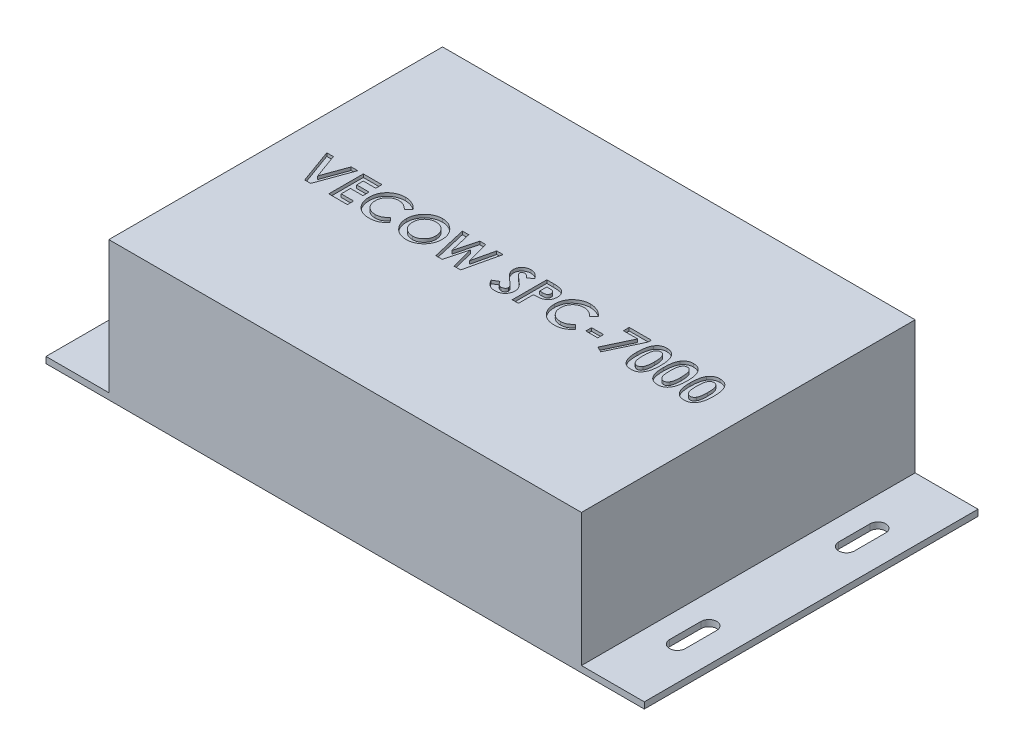
SolidWorks part; units mm, degrees
ref_plane "Front Plane" through (0, 0, 0) normal (0, 0, 1) x (1, 0, 0)
ref_plane "Top Plane" through (0, 0, 0) normal (0, 1, 0) x (1, 0, 0)
ref_plane "Right Plane" through (0, 0, 0) normal (1, 0, 0) x (0, 0, -1)
sketch "Sketch1" plane through (0, 0, 0) normal (0, 1, 0) x (1, 0, 0)
  line L1 (-75.2, 53.1) -> (75.2, 53.1)
  line L2 (-75.2, 53.1) -> (-75.2, -53.1)
  line L3 (-75.2, -53.1) -> (75.2, -53.1)
  line L4 (75.2, 53.1) -> (75.2, -53.1)
  line L5 (-75.2, 53.1) -> (75.2, -53.1) construction
  line L6 (-75.2, -53.1) -> (75.2, 53.1) construction
  point P0 (0, 0)
  dimension "D1" = 150.4
  dimension "D2" = 106.2
extrude "Boss-Extrude1" add sketch "Sketch1" along normal blind 44.2
sketch "Sketch2" plane through (75.2, 0, 0) normal (1, 0, 0) x (0, 0, -1)
  line L0 (53.1, 44.2) -> (53.1, 0) construction
  line L1 (-53.1, 0) -> (53.1, 0)
  line L2 (-53.1, 0) -> (-53.1, 2)
  line L3 (-53.1, 2) -> (53.1, 2)
  line L4 (53.1, 0) -> (53.1, 2)
  dimension "D1" = 2
extrude "Boss-Extrude2" add sketch "Sketch2" along normal blind 20
mirror "Mirror1" about plane through (0, 0, 0) normal (1, 0, 0) of "Boss-Extrude2"
sketch "Sketch3" plane through (0, 0, 0) normal (0, -1, 0) x (1, 0, 0)
  line L0 (-84.55, 31.9) -> (-84.55, 21.9) construction
  line L1 (-82.05, 31.9) -> (-82.05, 21.9)
  line L2 (-87.05, 31.9) -> (-87.05, 21.9)
  line L3 (-84.55, -21.9) -> (-84.55, -31.9) construction
  line L4 (-82.05, -21.9) -> (-82.05, -31.9)
  line L5 (-84.55, 26.9) -> (84.55, 26.9) construction
  line L6 (-84.55, 26.9) -> (-84.55, -26.9) construction
  line L7 (-84.55, -26.9) -> (84.55, -26.9) construction
  line L8 (84.55, 26.9) -> (84.55, -26.9) construction
  line L9 (-84.55, 26.9) -> (84.55, -26.9) construction
  line L10 (-84.55, -26.9) -> (84.55, 26.9) construction
  line L11 (-87.05, -21.9) -> (-87.05, -31.9)
  line L12 (84.55, 31.9) -> (84.55, 21.9) construction
  line L13 (87.05, 31.9) -> (87.05, 21.9)
  line L14 (82.05, 31.9) -> (82.05, 21.9)
  line L15 (84.55, -21.9) -> (84.55, -31.9) construction
  line L16 (87.05, -21.9) -> (87.05, -31.9)
  line L17 (82.05, -21.9) -> (82.05, -31.9)
  arc A0 (-82.05, 31.9) -> (-87.05, 31.9) centre (-84.55, 31.9) ccw
  arc A1 (-87.05, 21.9) -> (-82.05, 21.9) centre (-84.55, 21.9) ccw
  arc A2 (-82.05, -21.9) -> (-87.05, -21.9) centre (-84.55, -21.9) ccw
  arc A3 (-87.05, -31.9) -> (-82.05, -31.9) centre (-84.55, -31.9) ccw
  arc A4 (87.05, 31.9) -> (82.05, 31.9) centre (84.55, 31.9) ccw
  arc A5 (82.05, 21.9) -> (87.05, 21.9) centre (84.55, 21.9) ccw
  arc A6 (87.05, -21.9) -> (82.05, -21.9) centre (84.55, -21.9) ccw
  arc A7 (82.05, -31.9) -> (87.05, -31.9) centre (84.55, -31.9) ccw
  point P0 (0, 0)
  point P7 (-84.55, 26.9)
  point P14 (-84.55, -26.9)
  point P22 (84.55, 26.9)
  point P29 (84.55, -26.9)
  dimension "D3" = 2.5
  dimension "D1" = 169.1
  dimension "D2" = 53.8
  dimension "D4" = 10
extrude "Cut-Extrude1" cut sketch "Sketch3" against normal blind 20
sketch "Sketch4" plane through (0, 44.2, 0) normal (0, 1, 0) x (1, 0, 0)
  line L0 (-75.2, -5.5) -> (75.2, -5.5) construction
  line L1 (-75.2, 53.1) -> (-75.2, -53.1) construction
  line L2 (75.2, 53.1) -> (75.2, -53.1) construction
  text T0 "VECOW SPC-7000" font "Century Gothic" height 11
  dimension "D1" = 5.5
extrude "Cut-Extrude2" cut sketch "Sketch4" against normal blind 1
